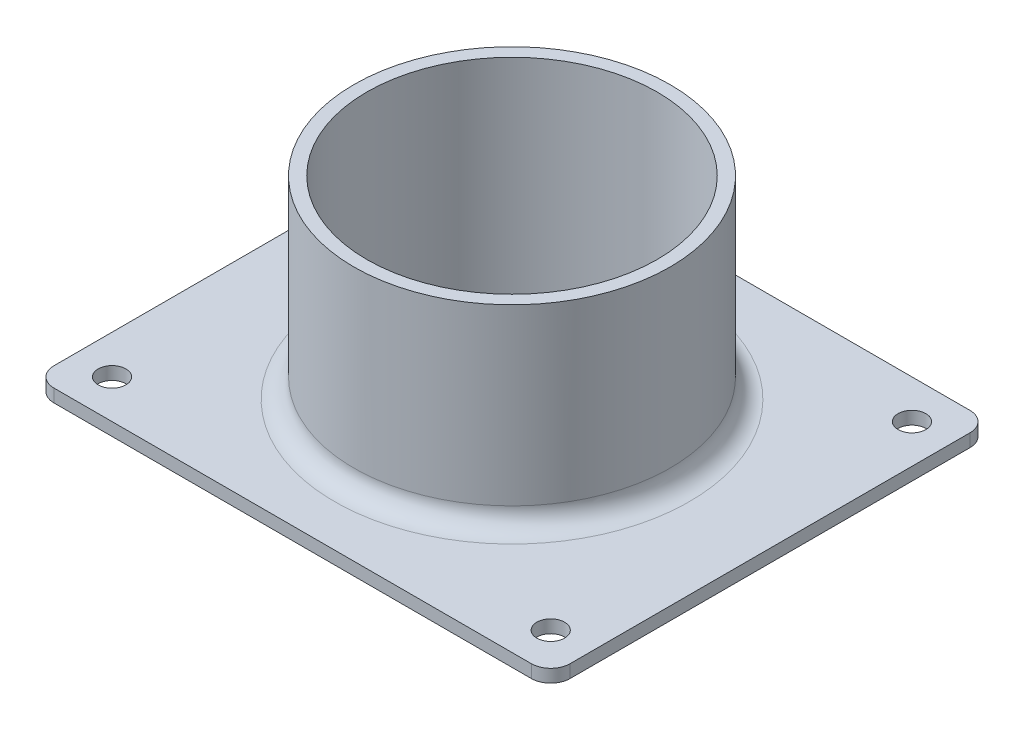
SolidWorks part; units mm, degrees
ref_plane "Front Plane" through (0, 0, 0) normal (0, 0, 1) x (1, 0, 0)
ref_plane "Top Plane" through (0, 0, 0) normal (0, 1, 0) x (1, 0, 0)
ref_plane "Right Plane" through (0, 0, 0) normal (1, 0, 0) x (0, 0, -1)
sketch "Sketch1" plane through (0, 0, 0) normal (0, 1, 0) x (1, 0, 0)
  line L0 (0, 34) -> (0, -34) construction
  line L1 (-40, -34) -> (40, -34)
  line L2 (-40, -34) -> (-40, 34)
  line L3 (-40, 34) -> (40, 34)
  line L4 (40, -34) -> (40, 34)
  line L5 (-40, -34) -> (40, 34) construction
  line L6 (-40, 34) -> (40, -34) construction
  line L7 (-40, 0) -> (40, 0) construction
  circle A0 centre (0, 0) radius 22.5
  circle A1 centre (0, 0) radius 24.5 construction
  circle A4 centre (34, 28) radius 2.15
  circle A5 centre (34, -28) radius 2.15
  circle A6 centre (-34, -28) radius 2.15
  circle A7 centre (-34, 28) radius 2.15
  point P0 (0, 0)
  dimension "D1" = 45
  dimension "D2" = 49
  dimension "D3" = 4.3
  dimension "D4" = 6
  dimension "D5" = 6
  dimension "D6" = 34
  dimension "D7" = 80
extrude "Boss-Extrude1" add sketch "Sketch1" along normal blind 2
sketch "Sketch2" plane through (0, 2, 0) normal (0, 1, 0) x (1, 0, 0)
  circle A0 centre (0, 0) radius 24.5 construction
  circle A1 centre (0, 0) radius 22.5 construction
  circle A3 centre (0, 0) radius 24.5
  circle A4 centre (0, 0) radius 22.5
extrude "Boss-Extrude2" add sketch "Sketch2" along normal blind 30
fillet "Fillet1" radius 3 1 edges at (0, 2, -24.5)
fillet "Fillet2" radius 3 4 edges at (40, 1, -34) (40, 1, 34) (-40, 1, 34) (-40, 1, -34)
